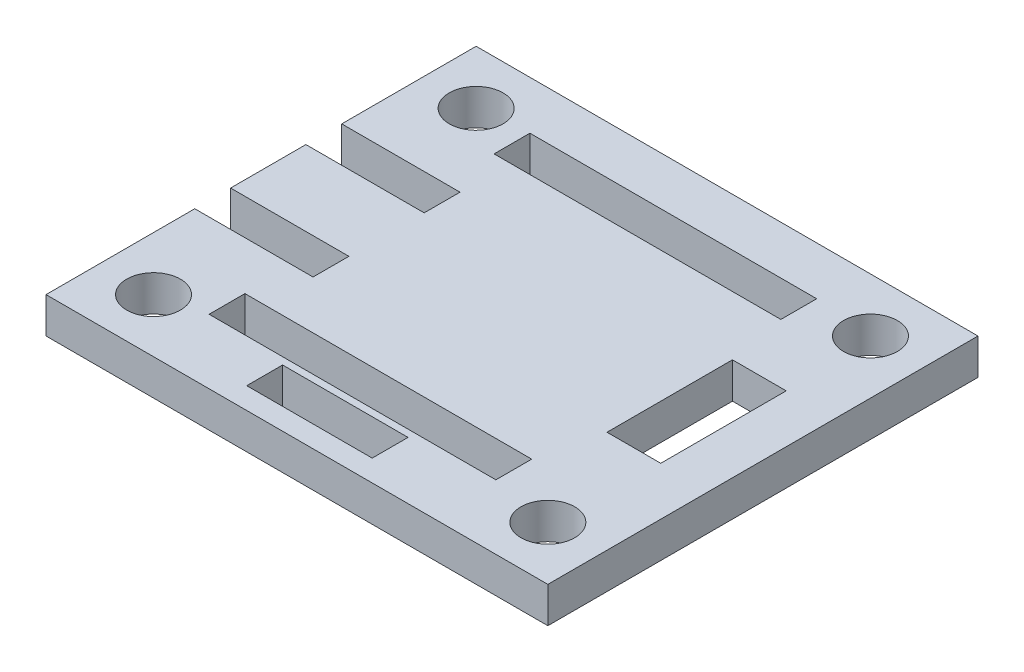
SolidWorks part; units mm, degrees
ref_plane "前视基准面" through (0, 0, 0) normal (0, 0, 1) x (1, 0, 0)
ref_plane "上视基准面" through (0, 0, 0) normal (0, 1, 0) x (1, 0, 0)
ref_plane "右视基准面" through (0, 0, 0) normal (1, 0, 0) x (0, 0, -1)
other "Configuration Table"
sketch "草图1" plane through (0, 0, 0) normal (0, 1, 0) x (1, 0, 0)
  line L1 (-28, 0) -> (0, 0)
  line L2 (-28, 0) -> (-28, -24)
  line L3 (-28, -24) -> (0, -24)
  line L4 (0, 0) -> (0, -24)
  line L5 (-18, -22.8) -> (-11, -22.8)
  line L6 (-18, -22.8) -> (-18, -20.8)
  line L7 (-18, -20.8) -> (-11, -20.8)
  line L8 (-11, -22.8) -> (-11, -20.8)
  line L9 (-5.7, -15) -> (-2.7, -15)
  line L10 (-5.7, -15) -> (-5.7, -8)
  line L11 (-5.7, -8) -> (-2.7, -8)
  line L12 (-2.7, -15) -> (-2.7, -8)
  line L13 (-22.3, -4.7) -> (-6.3, -4.7)
  line L14 (-22.3, -4.7) -> (-22.3, -2.7)
  line L15 (-22.3, -2.7) -> (-6.3, -2.7)
  line L16 (-6.3, -4.7) -> (-6.3, -2.7)
  line L17 (-21.4, -15.7) -> (-28, -15.7)
  line L18 (-21.4, -15.7) -> (-21.4, -13.7)
  line L19 (-21.4, -13.7) -> (-28, -13.7)
  line L20 (-28, -15.7) -> (-28, -13.7)
  line L21 (-21.4, -9.5) -> (-28, -9.5)
  line L22 (-21.4, -9.5) -> (-21.4, -7.5)
  line L23 (-21.4, -7.5) -> (-28, -7.5)
  line L24 (-28, -9.5) -> (-28, -7.5)
  line L25 (-22.5, -20.4) -> (-6.5, -20.4)
  line L26 (-22.5, -20.4) -> (-22.5, -18.4)
  line L27 (-22.5, -18.4) -> (-6.5, -18.4)
  line L28 (-6.5, -20.4) -> (-6.5, -18.4)
  circle A0 centre (-25, -3) radius 1.5
  circle A1 centre (-3, -3) radius 1.5
  circle A2 centre (-25, -21) radius 1.5
  circle A3 centre (-3, -21) radius 1.5
  dimension "D3" = 3
  dimension "D1" = 28
  dimension "D2" = 24
  dimension "D4" = 3
  dimension "D5" = 3
  dimension "D6" = 3
  dimension "D7" = 3
  dimension "D8" = 2
  dimension "D9" = 7.5
  dimension "D10" = 4.2
  dimension "D11" = 6.6
  dimension "D12" = 16
  dimension "D13" = 2.7
  dimension "D14" = 6.3
  dimension "D15" = 2
  dimension "D16" = 5.7
  dimension "D17" = 3
  dimension "D18" = 9
  dimension "D19" = 7
  dimension "D20" = 1.2
  dimension "D21" = 2
  dimension "D22" = 7
  dimension "D23" = 10
  dimension "D24" = 5.5
  dimension "D25" = 6.5
  dimension "D26" = 3.6
  dimension "D27" = 2
extrude "凸台-拉伸1" add sketch "草图1" along normal blind 2 contours L2 L3 L4 L1
extrude "切除-拉伸1" cut sketch "草图1<5>" along normal through all contours A2 | A3 | A0 | A1 | L19 L20 L17 L18 | L23 L24 L21 L22 | L15 L16 L13 L14 | L12 L11 L10 L9 | L7 L8 L5 L6 | L25 L28 L27 L26
sketch "草图1<5>" plane through (0, 0, 0) normal (0, 1, 0) x (1, 0, 0) same geometry as "草图1"
